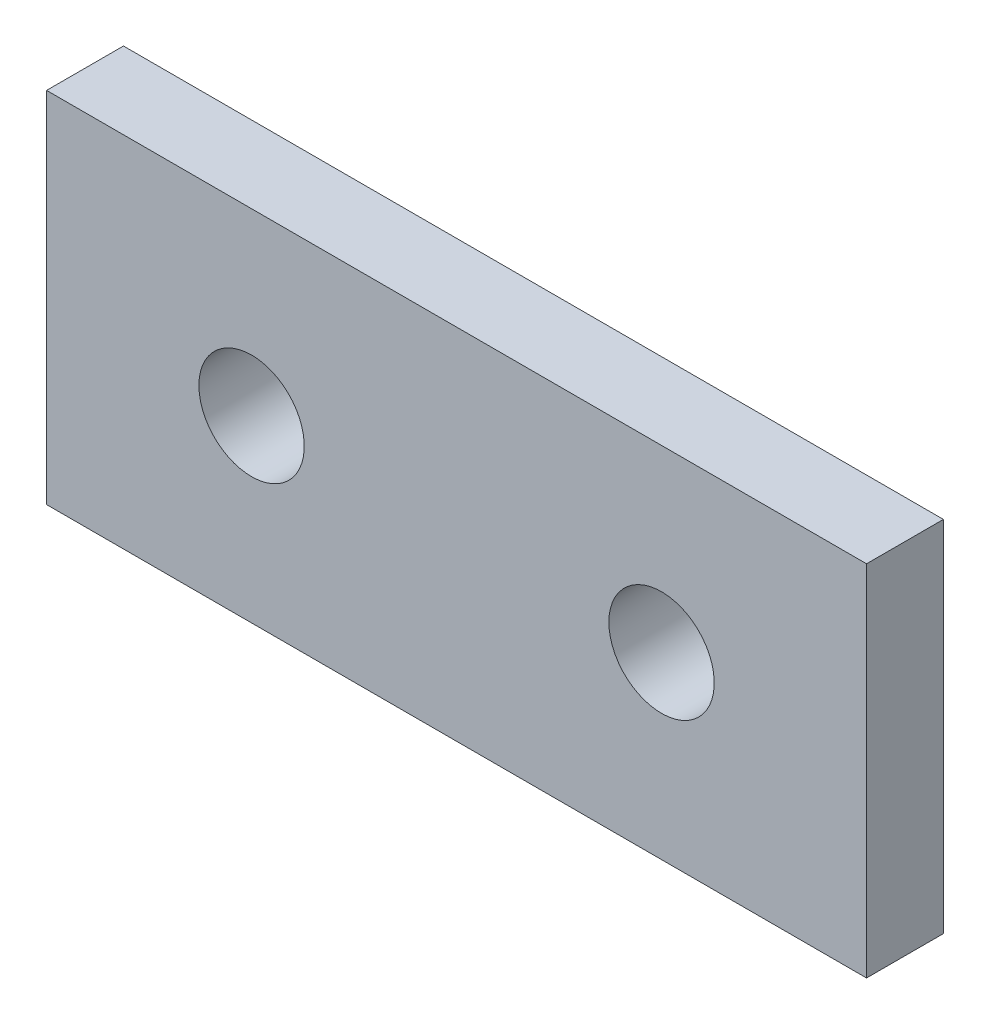
SolidWorks part; units mm, degrees
ref_plane "Front Plane" through (0, 0, 0) normal (0, 0, 1) x (1, 0, 0)
ref_plane "Top Plane" through (0, 0, 0) normal (0, 1, 0) x (1, 0, 0)
ref_plane "Right Plane" through (0, 0, 0) normal (1, 0, 0) x (0, 0, -1)
sketch "Sketch1" plane through (0, 0, 0) normal (0, 0, 1) x (1, 0, 0)
  line L0 (0, 0) -> (0, 22.225)
  line L1 (12.7, 11.1125) -> (38.1, 11.1125) construction
  line L4 (50.8, 22.225) -> (0, 22.225)
  line L5 (50.8, 0) -> (0, 0)
  line L7 (50.8, 22.225) -> (50.8, 0)
  circle A0 centre (12.7, 11.1125) radius 3.2639
  circle A1 centre (38.1, 11.1125) radius 3.2639
  dimension "D1" = 25.4
  dimension "E" = 6.5278
  dimension "D2" = 12.7
  dimension "C" = 22.225
  dimension "D3" = 11.1125
  dimension "B" = 50.8
extrude "Boss-Extrude1" add sketch "Sketch1" along normal mid plane 4.7625
ref_axis "Axis1" through (38.1, 11.1125, 2.3813) along (0, 0, -1)
ref_axis "Axis2" through (12.7, 11.1125, 2.3813) along (0, 0, -1)
